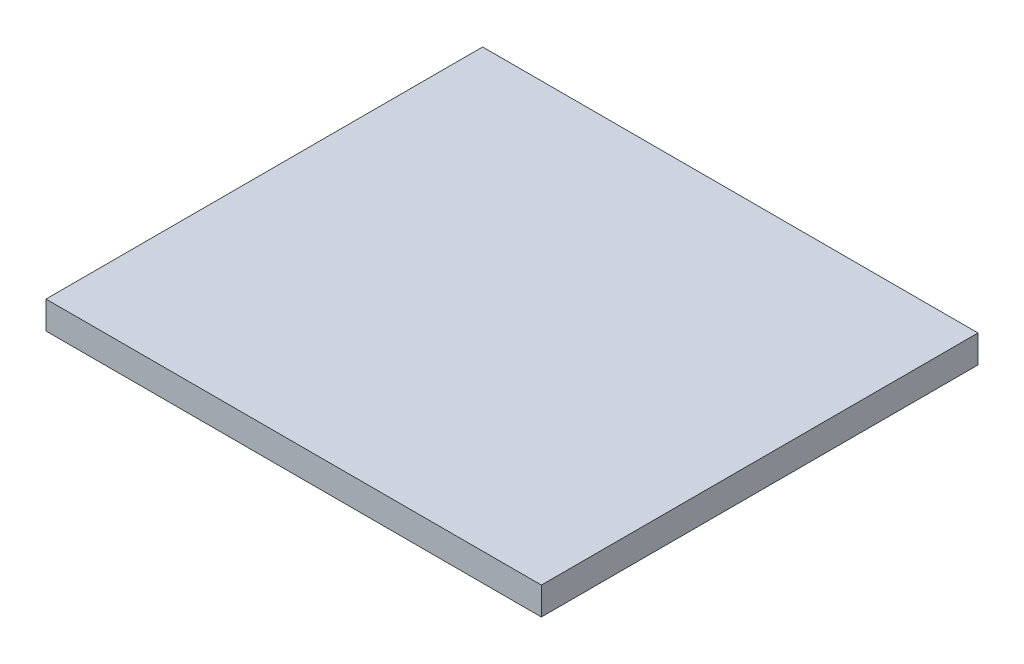
SolidWorks part; units mm, degrees
material "6061 Alloy"
ref_plane "Front Plane" through (0, 0, 0) normal (0, 0, 1) x (1, 0, 0)
ref_plane "Top Plane" through (0, 0, 0) normal (0, 1, 0) x (1, 0, 0)
ref_plane "Right Plane" through (0, 0, 0) normal (1, 0, 0) x (0, 0, -1)
sketch "Sketch1" plane through (0, 0, 0) normal (0, 1, 0) x (1, 0, 0)
  line L1 (0, 0) -> (113.538, 0)
  line L2 (0, 0) -> (0, 100.076)
  line L3 (0, 100.076) -> (113.538, 100.076)
  line L4 (113.538, 0) -> (113.538, 100.076)
  dimension "D1" = 100.076
  dimension "D2" = 113.538
extrude "Boss-Extrude1" add sketch "Sketch1" along normal blind 6.35
